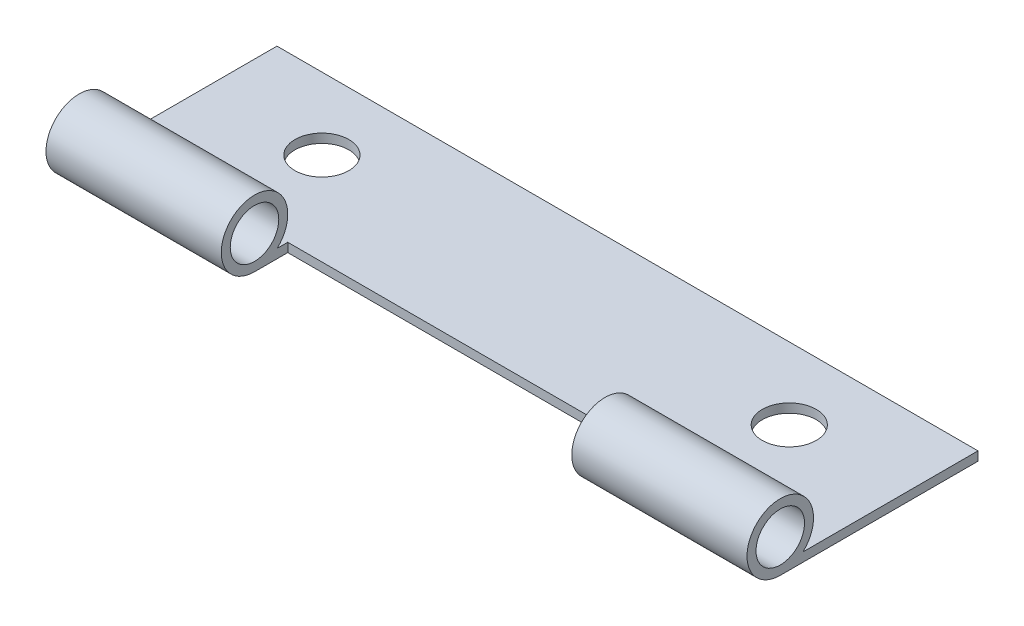
SolidWorks part; units mm, degrees
material "Latón"
ref_plane "Alzado" through (0, 0, 0) normal (0, 0, 1) x (1, 0, 0)
ref_plane "Planta" through (0, 0, 0) normal (0, 1, 0) x (1, 0, 0)
ref_plane "Vista lateral" through (0, 0, 0) normal (1, 0, 0) x (0, 0, -1)
sketch "Croquis1" plane through (0, 0, 0) normal (0, 1, 0) x (1, 0, 0)
  line L0 (0, 5.5) -> (0, -5.5) construction
  line L1 (-19.5, -5.5) -> (19.5, -5.5)
  line L2 (-19.5, -5.5) -> (-19.5, 5.5)
  line L3 (-19.5, 5.5) -> (19.5, 5.5)
  line L4 (19.5, -5.5) -> (19.5, 5.5)
  circle A0 centre (-13, 1.5) radius 1.5
  circle A1 centre (13, 1.5) radius 1.5
  dimension "D3" = 3
  dimension "D1" = 39
  dimension "D2" = 11
  dimension "D4" = 4
  dimension "D5" = 26
extrude "Saliente-Extruir1" add sketch "Croquis1" along normal blind 0.5
sketch "Croquis2" plane through (19.5, 0, 0) normal (1, 0, 0) x (0, 0, -1)
  circle A0 centre (-5.5, 1.85) radius 1.85
  circle A1 centre (-5.5, 1.85) radius 1.35
  dimension "D1" = 3.7
extrude "Saliente-Extruir2" add sketch "Croquis2" against normal up to surface (39 mm away) up to face at (-19.5, 0.25, 0)
sketch "Croquis3" plane through (0, 0, 0) normal (0, -1, 0) x (1, 0, 0)
  line L0 (19.5, 7.35) -> (-19.5, 7.35) construction
  line L1 (-9.75, 7.35) -> (9.75, 7.35)
  line L2 (-9.75, 7.35) -> (-9.75, 3.65)
  line L3 (-9.75, 3.65) -> (9.75, 3.65)
  line L4 (9.75, 7.35) -> (9.75, 3.65)
  line L5 (-19.5, 3.65) -> (19.5, 3.65) construction
  line L6 (-9.75, 5.5) -> (-19.5, 5.5) construction
  line L7 (9.75, 5.5) -> (19.5, 5.5) construction
  line L8 (19.5, 3.65) -> (19.5, 7.35) construction
  line L9 (-19.5, 7.35) -> (-19.5, 3.65) construction
  dimension "D1" = 19.5
extrude "Cortar-Extruir1" cut sketch "Croquis3" against normal through all
